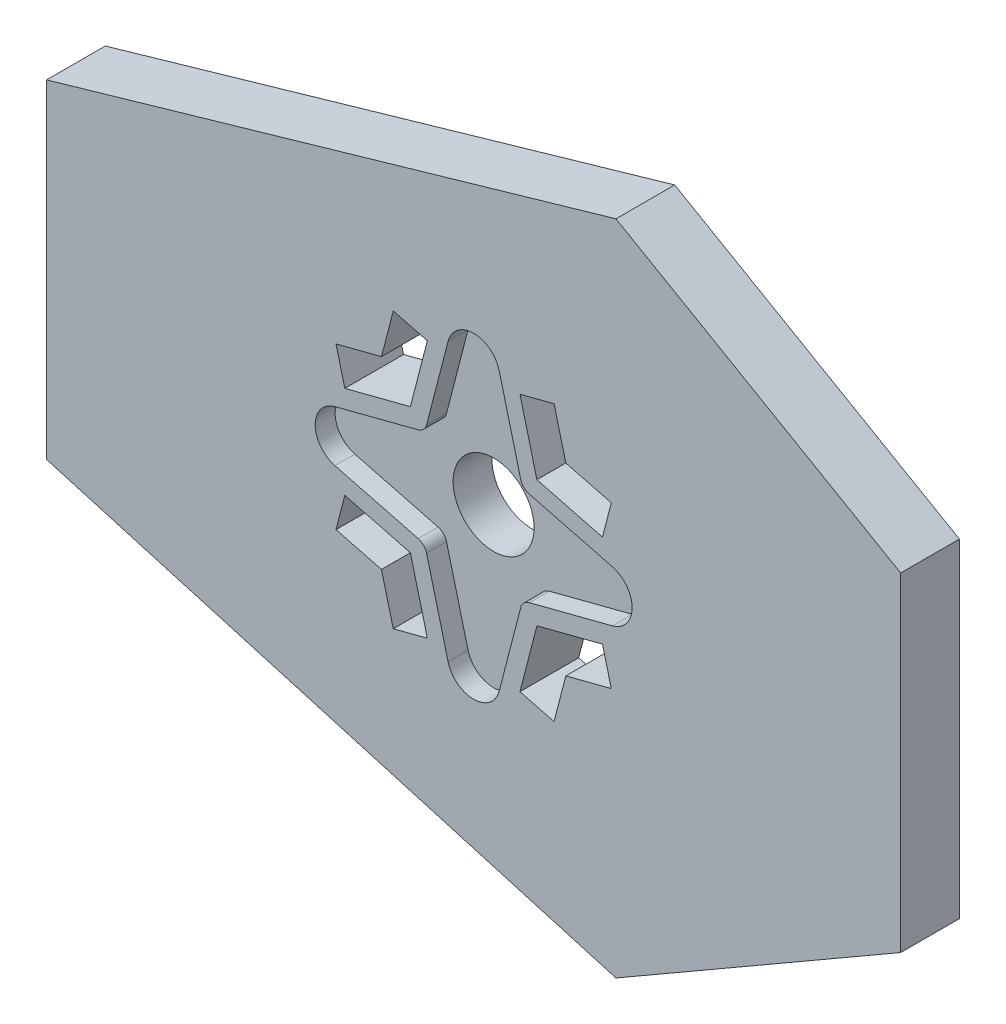
SolidWorks part; units mm, degrees
ref_plane "Front Plane" through (0, 0, 0) normal (0, 0, 1) x (1, 0, 0)
ref_plane "Top Plane" through (0, 0, 0) normal (0, 1, 0) x (1, 0, 0)
ref_plane "Right Plane" through (0, 0, 0) normal (1, 0, 0) x (0, 0, -1)
sketch "Sketch1" plane through (0, 0, 0) normal (0, 0, 1) x (1, 0, 0)
  line L0 (6.9744, -28) -> (-41.5231, -14) construction
  line L1 (-41.5231, 14) -> (-41.5231, -14) construction
  line L2 (-41.5231, 14) -> (6.9744, 28) construction
  line L3 (31.2231, 14) -> (6.9744, 28) construction
  line L4 (31.2231, -14) -> (31.2231, 14) construction
  line L5 (6.9744, -28) -> (31.2231, -14) construction
  line L6 (6.9744, -28) -> (-41.5231, -14)
  line L7 (-41.5231, 14) -> (-41.5231, -14)
  line L8 (-41.5231, 14) -> (6.9744, 28)
  line L9 (31.2231, 14) -> (6.9744, 28)
  line L10 (31.2231, -14) -> (31.2231, 14)
  line L11 (6.9744, -28) -> (31.2231, -14)
  line L20 (-2.9716, -11.813) -> (-1.1403, -4.7276)
  line L21 (-2.9716, -11.813) -> (-1.1403, -4.7276)
  line L22 (-0.4224, -4.0097) -> (6.663, -2.1784)
  line L23 (-0.4224, -4.0097) -> (6.663, -2.1784)
  line L24 (6.663, 2.1784) -> (-0.4224, 4.0097)
  line L25 (6.663, 2.1784) -> (-0.4224, 4.0097)
  line L26 (-1.1403, 4.7276) -> (-2.9716, 11.813)
  line L27 (-1.1403, 4.7276) -> (-2.9716, 11.813)
  line L28 (-7.3284, 11.813) -> (-9.1597, 4.7276)
  line L29 (-7.3284, 11.813) -> (-9.1597, 4.7276)
  line L30 (-9.8776, 4.0097) -> (-16.963, 2.1784)
  line L31 (-9.8776, 4.0097) -> (-16.963, 2.1784)
  line L32 (-16.963, -2.1784) -> (-9.8776, -4.0097)
  line L33 (-16.963, -2.1784) -> (-9.8776, -4.0097)
  line L34 (-9.1597, -4.7276) -> (-7.3284, -11.813)
  line L35 (-9.1597, -4.7276) -> (-7.3284, -11.813)
  circle A0 centre (-5.15, 0) radius 3.45 construction
  circle A1 centre (-5.15, 0) radius 3.45
  arc A9 (6.663, -2.1784) -> (6.663, 2.1784) centre (6.1, 0) ccw
  arc A11 (-2.9716, 11.813) -> (-7.3284, 11.813) centre (-5.15, 11.25) ccw
  arc A13 (-16.963, 2.1784) -> (-16.963, -2.1784) centre (-16.4, 0) ccw
  arc A15 (-7.3284, -11.813) -> (-2.9716, -11.813) centre (-5.15, -11.25) ccw
  arc A17 (6.663, -2.1784) -> (6.663, 2.1784) centre (6.1, 0) ccw
  arc A19 (-2.9716, 11.813) -> (-7.3284, 11.813) centre (-5.15, 11.25) ccw
  arc A21 (-16.963, 2.1784) -> (-16.963, -2.1784) centre (-16.4, 0) ccw
  arc A23 (-7.3284, -11.813) -> (-2.9716, -11.813) centre (-5.15, -11.25) ccw
  arc A30 (-0.4224, -4.0097) -> (-1.1403, -4.7276) centre (-0.1722, -4.9778) ccw
  arc A31 (-0.4224, -4.0097) -> (-1.1403, -4.7276) centre (-0.1722, -4.9778) ccw
  arc A32 (-1.1403, 4.7276) -> (-0.4224, 4.0097) centre (-0.1722, 4.9778) ccw
  arc A33 (-1.1403, 4.7276) -> (-0.4224, 4.0097) centre (-0.1722, 4.9778) ccw
  arc A34 (-9.8776, 4.0097) -> (-9.1597, 4.7276) centre (-10.1278, 4.9778) ccw
  arc A35 (-9.8776, 4.0097) -> (-9.1597, 4.7276) centre (-10.1278, 4.9778) ccw
  arc A36 (-9.1597, -4.7276) -> (-9.8776, -4.0097) centre (-10.1278, -4.9778) ccw
  arc A37 (-9.1597, -4.7276) -> (-9.8776, -4.0097) centre (-10.1278, -4.9778) ccw
  dimension "D1" = 0
extrude "Boss-Extrude1" add sketch "Sketch1" along normal up to surface (3.3 mm away) contours L8 L9 L10 L11 L6 L7 | A1
extrude "Boss-Extrude2" add sketch "Sketch1<3>" along normal up to surface (5 mm away) contours L6 L11 L10 L9 L8 L7 A23 A21 A19 A17 region at (-17.0197, -20.118, 0)
sketch "Sketch1<3>" plane through (0, 0, 0) normal (0, 0, 1) x (1, 0, 0) same geometry as "Sketch1"
sketch "Sketch3" plane through (0, 0, 5) normal (0, 0, 1) x (1, 0, 0)
  line L0 (-13.0004, 7.8504) -> (-16.8732, 6.8495) construction
  line L1 (-16.8732, 6.8495) -> (-16.1225, 3.9449) construction
  line L2 (-10.5382, 5.3882) -> (-16.1225, 3.9449) construction
  line L3 (-9.0949, 10.9725) -> (-10.5382, 5.3882) construction
  line L4 (-11.9995, 11.7232) -> (-9.0949, 10.9725) construction
  line L5 (-11.9995, 11.7232) -> (-13.0004, 7.8504) construction
  line L6 (-13.0004, 7.8504) -> (-16.8732, 6.8495)
  line L7 (-16.8732, 6.8495) -> (-16.1225, 3.9449)
  line L8 (-10.5382, 5.3882) -> (-16.1225, 3.9449)
  line L9 (-9.0949, 10.9725) -> (-10.5382, 5.3882)
  line L10 (-11.9995, 11.7232) -> (-9.0949, 10.9725)
  line L11 (-11.9995, 11.7232) -> (-13.0004, 7.8504)
extrude "Cut-Extrude1" cut sketch "Sketch3" against normal through all
sketch "Sketch4" plane through (0, 0, 5) normal (0, 0, 1) x (1, 0, 0)
  line L0 (-5.15, 13.5) -> (-5.15, -13.5) construction
  line L1 (-18.65, 0) -> (8.35, 0) construction
  arc A0 (-2.9716, 11.813) -> (-7.3284, 11.813) centre (-5.15, 11.25) ccw construction
  arc A1 (-7.3284, -11.813) -> (-2.9716, -11.813) centre (-5.15, -11.25) ccw construction
  arc A2 (-16.963, 2.1784) -> (-16.963, -2.1784) centre (-16.4, 0) ccw construction
  arc A3 (6.663, -2.1784) -> (6.663, 2.1784) centre (6.1, 0) ccw construction
ref_plane "Plane1" through (-5.15, 0, 0) normal (-1, 0, 0) x (0, -1, 0)
ref_plane "Plane2" through (0, 0, 0) normal (0, -1, 0) x (1, 0, 0)
mirror "Mirror1" about plane through (-5.15, 0, 0) normal (-1, 0, 0) of "Cut-Extrude1"
mirror "Mirror2" about plane through (0, 0, 0) normal (0, -1, 0) of "Cut-Extrude1", "Mirror1"
